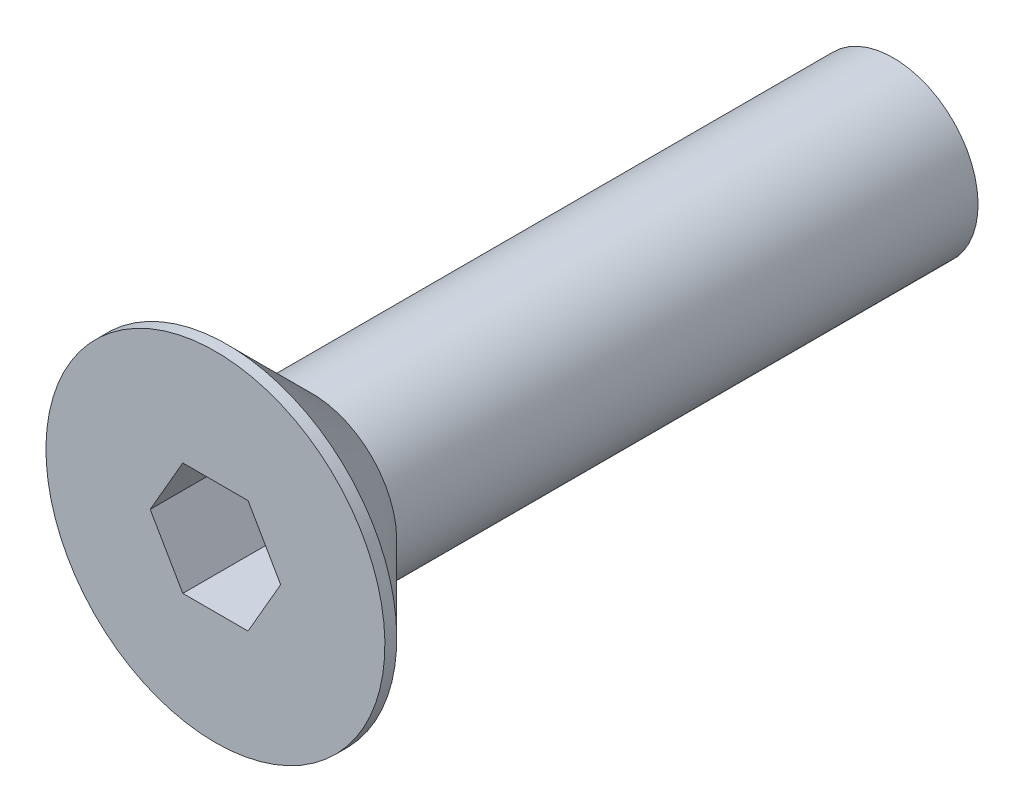
SolidWorks part; units mm, degrees
material "Alloy Steel"
ref_plane "Front Plane" through (0, 0, 0) normal (0, 0, 1) x (1, 0, 0)
ref_plane "Top Plane" through (0, 0, 0) normal (0, 1, 0) x (1, 0, 0)
ref_plane "Right Plane" through (0, 0, 0) normal (1, 0, 0) x (0, 0, -1)
ref_axis "Axis1" through (0, 0, -52.8182) along (0, 0, 1)
ref_axis "Axis2" through (0, -15.5981, 0) along (0, 1, 0)
ref_axis "Axis3" through (-12.2581, 0, 0) along (1, 0, 0)
sketch "Sketch1" plane through (0, 0, 0) normal (1, 0, 0) x (0, 0, -1)
  line L0 (-1.7, 0) -> (-1.7, 3)
  line L1 (-1.7, 3) -> (-1.49, 3)
  line L2 (0, 1.51) -> (0, 1.5)
  line L3 (0, 1.5) -> (10.3, 1.5)
  line L4 (10.3, 1.5) -> (10.3, 0)
  line L5 (10.3, 0) -> (-1.7, 0)
  line L6 (-5.5849, 0) -> (13.8966, 0) construction
  line L7 (0, 1.51) -> (-1.49, 3)
  dimension "D1" = 3
  dimension "D2" = 6
  dimension "D3" = 1.7
  dimension "D4" = 45
  dimension "D5" = 0.01
  dimension "LENGTH" = 12
revolve "Revolve1" add sketch "Sketch1" angle 360 about L6
cosmetic thread "Cosmetic Thread1"
sketch "Sketch2" plane through (0, 0, 1.7) normal (0, 0, 1) x (1, 0, 0)
  line L1 (0.5774, -1) -> (1.1547, 0)
  line L2 (1.1547, 0) -> (0.5774, 1)
  line L3 (0.5774, 1) -> (-0.5774, 1)
  line L4 (-0.5774, 1) -> (-1.1547, 0)
  line L5 (-1.1547, 0) -> (-0.5774, -1)
  line L6 (-0.5774, -1) -> (0.5774, -1)
  circle A0 centre (0, 0) radius 1 construction
  dimension "D1" = 2
extrude "Cut-Extrude1" cut sketch "Sketch2" against normal blind 1.5
